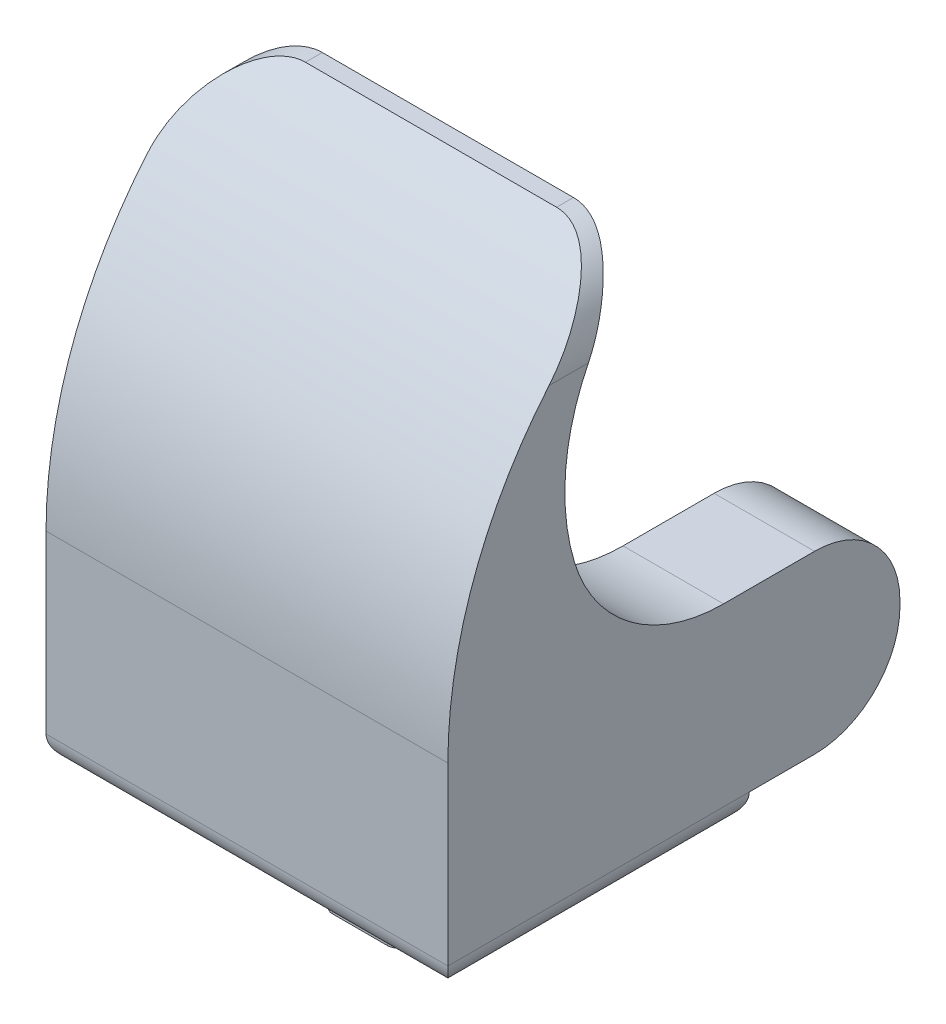
SolidWorks part; units mm, degrees
ref_plane "Front Plane" through (0, 0, 0) normal (0, 0, 1) x (1, 0, 0)
ref_plane "Top Plane" through (0, 0, 0) normal (0, 1, 0) x (1, 0, 0)
ref_plane "Right Plane" through (0, 0, 0) normal (1, 0, 0) x (0, 0, -1)
sketch "Sketch1" plane through (0, 0, 0) normal (0, 1, 0) x (1, 0, 0)
  line L1 (40, 30) -> (-40, 30)
  line L2 (40, 30) -> (40, -30)
  line L3 (40, -30) -> (-40, -30)
  line L4 (-40, 30) -> (-40, -30)
  line L5 (40, 30) -> (-40, -30) construction
  line L6 (40, -30) -> (-40, 30) construction
  point P0 (0, 0)
extrude "Boss-Extrude1" add sketch "Sketch1" along normal blind 40
sketch "Sketch2" plane through (0, 40, 0) normal (0, 1, 0) x (1, 0, 0)
  line L1 (-40, -30) -> (40, -30)
  line L2 (-40, -30) -> (-40, 10)
  line L3 (-40, 10) -> (40, 10)
  line L4 (40, -30) -> (40, 10)
extrude "Boss-Extrude2" add sketch "Sketch2" along normal blind 70
sketch "Sketch3" plane through (40, 0, 0) normal (1, 0, 0) x (0, 0, -1)
  line L1 (10, 40) -> (-30, 40) construction
  line L2 (10, 40) -> (10, 110)
  line L3 (10, 110) -> (-30, 110)
  line L4 (-30, 40) -> (-30, 110)
  arc A0 (10, 40) -> (10, 110) centre (38.2843, 75) cw
  arc A1 (-30, 40) -> (6.6434, 110) centre (55.1823, 40) cw
extrude "Cut-Extrude1" cut sketch "Sketch3" against normal up to next
fillet "Fillet4" radius 31 1 edges at (0, 40, -10)
fillet "Fillet6" radius 5 4 edges at (0, 0, 30) (40, 0, 0) (0, 0, -30) (-40, 0, 0)
fillet "Fillet7" radius 15 2 edges at (-40, 110, -8.3217) (40, 110, -8.3217)
sketch "Sketch5" plane through (0, 0, -30) normal (0, 0, -1) x (-1, 0, 0)
  line L0 (-40, 40) -> (40, 40) construction
  line L1 (-40, 5) -> (-20, 5)
  line L2 (-40, 5) -> (-40, 40)
  line L3 (-40, 40) -> (-20, 40)
  line L4 (-20, 5) -> (-20, 40)
extrude "Boss-Extrude4" add sketch "Sketch5" along normal blind 30
fillet "Fillet8" radius 17 2 edges at (30, 5, -60) (30, 40, -60)
fillet "Fillet9" radius 37 1 edges at (-10, 40, -30)
sketch "Sketch6" plane through (0, 0, 0) normal (0, -1, 0) x (1, 0, 0)
  line L1 (7.5, 7.5) -> (-7.5, 7.5)
  line L2 (7.5, 7.5) -> (7.5, -7.5)
  line L3 (7.5, -7.5) -> (-7.5, -7.5)
  line L4 (-7.5, 7.5) -> (-7.5, -7.5)
  line L5 (7.5, 7.5) -> (-7.5, -7.5) construction
  line L6 (7.5, -7.5) -> (-7.5, 7.5) construction
  point P0 (0, 0)
extrude "Boss-Extrude5" add sketch "Sketch6" along normal blind 20
fillet "Fillet10" radius 2 4 edges at (-7.5, -10, -7.5) (-7.5, -10, 7.5) (7.5, -10, -7.5) (7.5, -10, 7.5)
